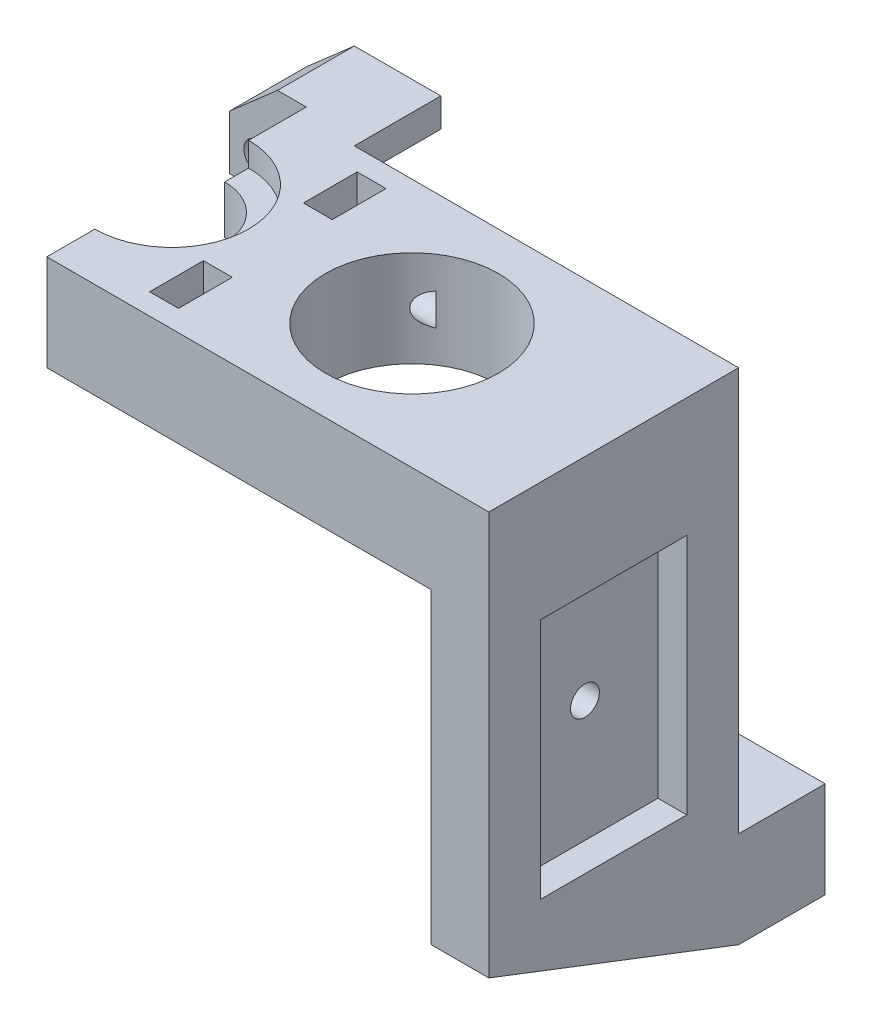
SolidWorks part; units mm, degrees
material "ABS"
ref_plane "Plano frontal" through (0, 0, 0) normal (0, 0, 1) x (1, 0, 0)
ref_plane "Plano superior" through (0, 0, 0) normal (0, 1, 0) x (1, 0, 0)
ref_plane "Plano direito" through (0, 0, 0) normal (1, 0, 0) x (0, 0, -1)
sketch "Esboço1" plane through (0, 0, 0) normal (0, 0, 1) x (1, 0, 0)
  line L0 (0, 0) -> (-6, 0)
  line L2 (0, 52) -> (0, 0)
  line L5 (-46, 42) -> (-6, 42)
  line L6 (-46, 42) -> (-46, 52)
  line L7 (-46, 52) -> (0, 52)
  line L8 (-6, 42) -> (-6, 0)
  point P0 (0, 0)
  point P4 (0, 0)
  point P13 (-11.65, 30)
  dimension "D3" = 6
  dimension "D7" = 10
  dimension "D1" = 40
  dimension "D2" = 52
extrude "Ressalto-extrusão1" add sketch "Esboço1" along normal blind 26
sketch "Esboço3" plane through (-46, 0, 0) normal (-1, 0, 0) x (0, 0, 1)
  line L0 (13, 52) -> (13, 42) construction
  line L1 (26, 52) -> (0, 52) construction
  line L3 (13, 52) -> (21, 52)
  line L4 (21, 52) -> (21, 49.5)
  line L5 (21, 49.5) -> (18.5, 49.5)
  line L6 (18.5, 49.5) -> (18.5, 44.5)
  line L7 (18.5, 44.5) -> (21, 44.5)
  line L8 (21, 44.5) -> (21, 42)
  line L10 (21, 42) -> (13, 42)
  line L11 (13, 52) -> (13, 42)
  point P6 (18.5, 47)
  dimension "D1" = 5
  dimension "D2" = 5.5
  dimension "D3" = 8
  dimension "D4" = 2.5
revolve "Corte-Revolução1" cut sketch "Esboço3" angle 360 about L0
sketch "Esboço4" plane through (-46, 0, 0) normal (-1, 0, 0) x (0, 0, 1)
  line L0 (13, 28) -> (13, -18.4674) construction
  line L2 (21, 52) -> (5, 52) construction
  line L3 (7.5, 49.5) -> (7.5, 44.5) construction
  circle A0 centre (5, 47) radius 1.75
  circle A1 centre (21, 47) radius 1.75
  point P6 (13, 28)
  point P7 (13, 52)
  point P11 (7.5, 47)
  dimension "D2" = 3.5
  dimension "D1" = 16
extrude "Corte-extrusão1" cut sketch "Esboço4" against normal blind 20
sketch "Esboço7" plane through (0, 52, 0) normal (0, 1, 0) x (1, 0, 0)
  line L0 (-46, -26) -> (-46, -21) construction
  circle A0 centre (-21, -13) radius 9
  arc A1 (-46, -21) -> (-46, -5) centre (-46, -13) ccw construction
  point P6 (-38, -13)
  point P9 (-46, -23.5)
  dimension "D1" = 18
  dimension "D2" = 25
extrude "Corte-extrusão3" cut sketch "Esboço7" against normal blind 10
sketch "Esboço10" plane through (0, 0, 0) normal (1, 0, 0) x (0, 0, -1)
  line L0 (-26, 52) -> (0, 52) construction
  line L5 (-20.6, 39.6) -> (-5.4, 39.6)
  line L6 (-20.6, 39.6) -> (-20.6, 14.4)
  line L7 (-20.6, 14.4) -> (-5.4, 14.4)
  line L8 (-5.4, 39.6) -> (-5.4, 14.4)
  line L9 (-20.6, 39.6) -> (-5.4, 14.4) construction
  line L10 (-20.6, 14.4) -> (-5.4, 39.6) construction
  point P0 (0, 0)
  point P3 (-13, 52)
  point P6 (-13, 27)
  point P11 (0, 0)
  dimension "D3" = 25
  dimension "D1" = 25.2
  dimension "D2" = 15.2
extrude "Corte-extrusão6" cut sketch "Esboço10" against normal blind 3
sketch "Esboço11" plane through (-3, 0, 0) normal (1, 0, 0) x (0, 0, -1)
  line L0 (-5.4, 39.6) -> (-20.6, 39.6) construction
  line L1 (-20.6, 39.6) -> (-20.6, 14.4) construction
  line L2 (0, 0) -> (-26, 10)
  line L3 (-26, 0) -> (-26, 52) construction
  line L4 (-26, 10) -> (-26, 0)
  line L5 (-26, 0) -> (0, 0)
  circle A0 centre (-13, 27) radius 1.5
  point P4 (-13, 39.6)
  point P8 (-20.6, 27)
  dimension "D1" = 3
  dimension "D2" = 10
extrude "Corte-extrusão7" cut sketch "Esboço11" against normal through all both and the other way through all
sketch "Esboço12" plane through (0, 0, 0) normal (0, 0, -1) x (-1, 0, 0)
  line L0 (0, 52) -> (46, 52) construction
  line L1 (0, 0) -> (16, 0)
  line L2 (0, 0) -> (0, 10)
  line L3 (0, 10) -> (10.5269, 10)
  line L4 (16, 0) -> (16, 5.5304)
  line L5 (40, 52) -> (49, 52)
  line L6 (40, 52) -> (40, 49)
  line L7 (48, 42) -> (54, 42)
  line L8 (54, 47.625) -> (54, 42)
  line L10 (46, 52) -> (46, 42) construction
  line L11 (48, 42) -> (40, 49)
  line L12 (46, 42) -> (6, 42) construction
  line L13 (10.5269, 10) -> (16, 5.5304)
  line L14 (49, 52) -> (54, 47.625)
  circle A0 centre (11, 5) radius 1.5
  circle A1 centre (51, 45) radius 1.5
  point P1 (0, 0)
  point P7 (0, 0)
  point P8 (0, 0)
  point P13 (48.7123, 52)
  dimension "D7" = 3
  dimension "D10" = 3
  dimension "D2" = 16
  dimension "D3" = 6
  dimension "D4" = 8
  dimension "D5" = 5
  dimension "D6" = 5
  dimension "D8" = 6
  dimension "D9" = 3
  dimension "D11" = 3
  dimension "D12" = 10
  dimension "D13" = 7
  dimension "D14" = 9
extrude "Ressalto-extrusão3" add sketch "Esboço12" along normal blind 9
sketch "Esboço5" plane through (0, 52, 0) normal (0, 1, 0) x (1, 0, 0)
  line L0 (-46, -5) -> (-36, -5) construction
  line L1 (-46, -5) -> (-46, 0) construction
  line L2 (-37.5, -2.2) -> (-34.5, -2.2)
  line L3 (-37.5, -2.2) -> (-37.5, -7.8)
  line L4 (-37.5, -7.8) -> (-34.5, -7.8)
  line L5 (-34.5, -2.2) -> (-34.5, -7.8)
  line L6 (-37.5, -2.2) -> (-34.5, -7.8) construction
  line L7 (-37.5, -7.8) -> (-34.5, -2.2) construction
  line L8 (-46, -13) -> (-16.3815, -13) construction
  line L9 (-37.5, -18.2) -> (-34.5, -23.8) construction
  line L10 (-37.5, -23.8) -> (-34.5, -18.2) construction
  line L11 (-46, -21) -> (-36, -21) construction
  line L12 (-34.5, -23.8) -> (-34.5, -18.2)
  line L13 (-37.5, -18.2) -> (-34.5, -18.2)
  line L14 (-37.5, -23.8) -> (-37.5, -18.2)
  line L15 (-37.5, -23.8) -> (-34.5, -23.8)
  line L16 (-54, 9) -> (-54, 0) construction
  line L17 (-46, 0) -> (-54, 0)
  line L18 (-46, 0) -> (-46, 1)
  line L19 (-46, 1) -> (-54, 1)
  line L20 (-54, 0) -> (-54, 1)
  dimension "D1" = 10
  dimension "D2" = 5.6
  dimension "D3" = 3
  dimension "D4" = 16
  dimension "D5" = 1
extrude "Corte-extrusão2" cut sketch "Esboço5" against normal blind 25
